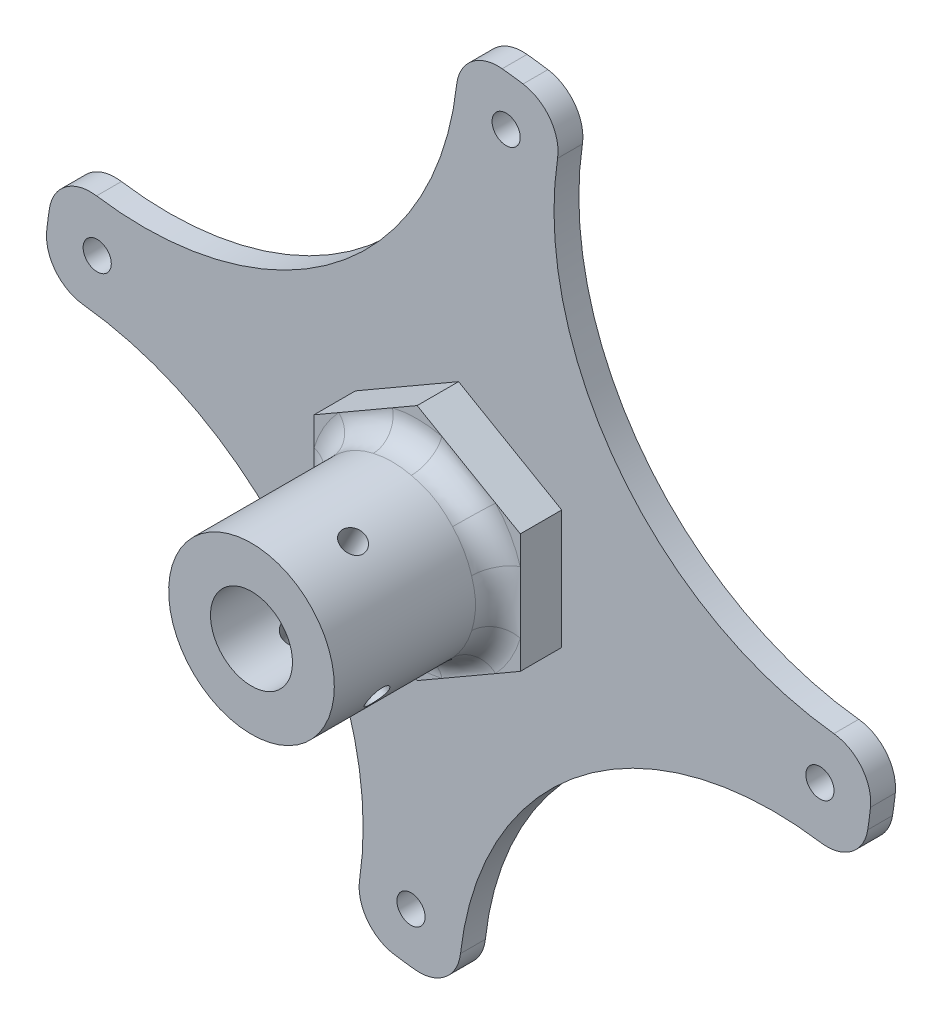
SolidWorks part; units mm, degrees
ref_plane "Front Plane" through (0, 0, 0) normal (0, 0, 1) x (1, 0, 0)
ref_plane "Top Plane" through (0, 0, 0) normal (0, 1, 0) x (1, 0, 0)
ref_plane "Right Plane" through (0, 0, 0) normal (1, 0, 0) x (0, 0, -1)
sketch "Sketch1" plane through (0, 0, 0) normal (0, 0, 1) x (1, 0, 0)
  circle A0 centre (0, 0) radius 50
  dimension "D1" = 100
extrude "Boss-Extrude1" add sketch "Sketch1" along normal blind 3
sketch "Sketch2" plane through (0, 0, 3) normal (0, 0, 1) x (1, 0, 0)
  line L1 (12.45, -7.188) -> (12.45, 7.188)
  line L2 (12.45, 7.188) -> (0, 14.376)
  line L3 (0, 14.376) -> (-12.45, 7.188)
  line L4 (-12.45, 7.188) -> (-12.45, -7.188)
  line L5 (-12.45, -7.188) -> (0, -14.376)
  line L6 (0, -14.376) -> (12.45, -7.188)
  circle A0 centre (0, 0) radius 12.45 construction
  dimension "D1" = 24.9
extrude "Boss-Extrude2" add sketch "Sketch2" along normal blind 5
sketch "Sketch3" plane through (0, 0, 8) normal (0, 0, 1) x (1, 0, 0)
  circle A0 centre (0, 0) radius 10
  dimension "D1" = 20
extrude "Boss-Extrude3" add sketch "Sketch3" along normal blind 20
fillet "Fillet1" radius 3 1 edges at (10, 0, 8)
sketch "Sketch4" plane through (0, 0, 28) normal (0, 0, 1) x (1, 0, 0)
  circle A0 centre (0, 0) radius 4.95
  dimension "D1" = 9.9
extrude "Cut-Extrude1" cut sketch "Sketch4" against normal through all
hole_wizard "Ø1.0mm Dowel Hole1" positions "3DSketch1" profile "Sketch5" hole size "Ø1.0" standard "ANSI Metric"
sketch3d "3DSketch1"
  point P0 (-8.6665, 4.9891, 21.4992)
  point P2 (4.7386, 8.806, 20.4576)
  point P4 (4.7386, 8.806, 20.4576)
  point P5 (0, 0, 19.4444)
sketch "Sketch5" plane through (-8.6665, 4.9891, 21.4992) normal (0, 0, 1) x (-0.4989, -0.8667, 0)
  line L0 (0, 0) -> (0, 34)
  line L1 (0, 34) -> (1.4, 33.1588)
  line L2 (1.4, 33.1588) -> (1.4, 0)
  line L5 (1.4, 0) -> (0, 0)
  line L10 (0, 34) -> (-1.4, 33.1588) construction
  line L11 (0, -6.35) -> (0, 107.95) construction
  dimension "Hole Dia." = 2.8
  dimension "Hole Depth" = 34
  dimension "Drill Angle" = 118
sketch "Sketch6" plane through (0, 0, 3) normal (0, 0, 1) x (1, 0, 0)
  line L0 (-50, 0) -> (0, 0)
  line L1 (0, 0) -> (-48.2963, 12.941)
  arc A0 (0, 50) -> (-48.2963, 12.941) centre (-37.997, 49.5186) cw
  circle A1 centre (0, 0) radius 50 construction
  arc A2 (-48.2963, 12.941) -> (0, 50) centre (0, 0) ccw
  arc A3 (50, 0) -> (12.941, 48.2963) centre (49.5186, 37.997) cw
  arc A4 (0, -50) -> (48.2963, -12.941) centre (37.997, -49.5186) cw
  arc A5 (-50, 0) -> (-12.941, -48.2963) centre (-49.5186, -37.997) cw
  point P21 (0, 0)
  circle M9 centre (0, 0) radius 50
  dimension "D1" = 38
  dimension "D3" = 4
  dimension "15" = 15
extrude "Cut-Extrude2" cut sketch "Sketch6" against normal blind 25 contours A0 L1 M9 | A3 A2 | A4 A2 | A5 L0 M9 region at (-29.8164, -22.879, 3) region at (-22.8789, 29.8165, 3) region at (22.879, -29.8164, 3) region at (29.8164, 22.879, 3)
fillet "Fillet2" radius 5 8 edges at (-48.2963, 12.941, 1.5) (-50, 0, 1.5) (-12.941, -48.2963, 1.5) (0, -50, 1.5) (48.2963, -12.941, 1.5) (50, 0, 1.5) (0, 50, 1.5) (12.941, 48.2963, 1.5)
sketch "Sketch7" plane through (0, 0, 0) normal (0, 0, -1) x (-1, 0, 0)
  line L0 (-6.5263, 49.5722) -> (0, 0) construction
  arc A0 (-5.2642, 49.7221) -> (-7.7842, 49.3903) centre (0, 0) ccw construction
  point P0 (-5.7432, 43.6236)
  point P10 (43.6236, 5.7432)
  point P11 (5.7432, -43.6236)
  point P12 (-43.6236, -5.7432)
  point P13 (0, 0)
  dimension "D1" = 6
  dimension "D2" = 4
hole_wizard "Ø1.0mm Dowel Hole2" positions "3DSketch2" profile "Sketch8" hole size "Ø1.0" standard "ANSI Metric"
sketch3d "3DSketch2"
  point P0 (5.7432, 43.6236, 0)
  point P3 (-43.6236, 5.7432, 0)
  point P6 (-5.7432, -43.6236, 0)
  point P9 (43.6236, -5.7432, 0)
sketch "Sketch8" plane through (5.7432, 43.6236, 0) normal (1, 0, 0) x (0, 1, 0)
  line L0 (0, 0) -> (0, 34)
  line L1 (0, 34) -> (1.7, 32.9785)
  line L2 (1.7, 32.9785) -> (1.7, 0)
  line L5 (1.7, 0) -> (0, 0)
  line L10 (0, 34) -> (-1.7, 32.9785) construction
  line L11 (0, -6.35) -> (0, 107.95) construction
  dimension "Hole Dia." = 3.4
  dimension "Hole Depth" = 34
  dimension "Drill Angle" = 118
